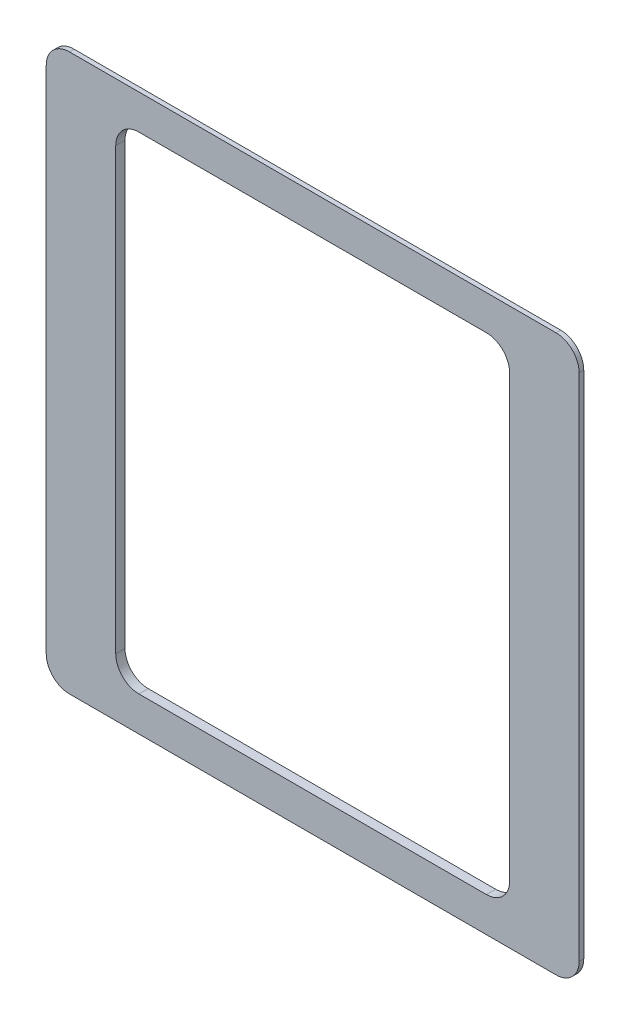
SolidWorks part; units mm, degrees
ref_plane "Front Plane" through (0, 0, 0) normal (0, 0, 1) x (1, 0, 0)
ref_plane "Top Plane" through (0, 0, 0) normal (0, 1, 0) x (1, 0, 0)
ref_plane "Right Plane" through (0, 0, 0) normal (1, 0, 0) x (0, 0, -1)
sketch "Sketch1" plane through (0, 0, 0) normal (0, 0, 1) x (1, 0, 0)
  line L1 (115, 120) -> (-115, 120)
  line L2 (115, 120) -> (115, -120)
  line L3 (115, -120) -> (-115, -120)
  line L4 (-115, 120) -> (-115, -120)
  line L5 (115, 120) -> (-115, -120) construction
  line L6 (115, -120) -> (-115, 120) construction
  line L7 (85, 105) -> (-85, 105)
  line L8 (85, 105) -> (85, -105)
  line L9 (85, -105) -> (-85, -105)
  line L10 (-85, 105) -> (-85, -105)
  line L11 (85, 105) -> (-85, -105) construction
  line L12 (85, -105) -> (-85, 105) construction
  point P0 (0, 0)
  point P6 (0, 0)
  dimension "D1" = 230
  dimension "D2" = 240
  dimension "D3" = 210
  dimension "D4" = 170
extrude "Boss-Extrude1" add sketch "Sketch1" along normal blind 2
fillet "Fillet1" radius 10 8 edges at (115, 120, 1) (85, 105, 1) (-85, 105, 1) (85, -105, 1) (-85, -105, 1) (-115, -120, 1) (115, -120, 1) (-115, 120, 1)
sketch "Sketch2" plane through (0, 0, 0) normal (0, 0, -1) x (-1, 0, 0)
  line L0 (75, -105) -> (-75, -105) construction
  line L1 (85, 95) -> (85, -95) construction
  line L2 (-75, 105) -> (75, 105) construction
  line L3 (-85, -95) -> (-85, 95) construction
  line L4 (75, -105) -> (-75, -105)
  line L5 (85, 95) -> (85, -95)
  line L6 (-75, 105) -> (75, 105)
  line L7 (-85, -95) -> (-85, 95)
  line L8 (75, -108) -> (-75, -108)
  line L9 (-88, -95) -> (-88, 95)
  line L10 (-75, 108) -> (75, 108)
  line L11 (88, 95) -> (88, -95)
  arc A0 (-85, -95) -> (-75, -105) centre (-75, -95) ccw construction
  arc A1 (75, -105) -> (85, -95) centre (75, -95) ccw construction
  arc A2 (85, 95) -> (75, 105) centre (75, 95) ccw construction
  arc A3 (-75, 105) -> (-85, 95) centre (-75, 95) ccw construction
  arc A4 (-85, -95) -> (-75, -105) centre (-75, -95) ccw
  arc A5 (75, -105) -> (85, -95) centre (75, -95) ccw
  arc A6 (85, 95) -> (75, 105) centre (75, 95) ccw
  arc A7 (-75, 105) -> (-85, 95) centre (-75, 95) ccw
  arc A8 (-88, -95) -> (-75, -108) centre (-75, -95) ccw
  arc A9 (-75, 108) -> (-88, 95) centre (-75, 95) ccw
  arc A10 (88, 95) -> (75, 108) centre (75, 95) ccw
  arc A11 (75, -108) -> (88, -95) centre (75, -95) ccw
  dimension "D1" = 3
extrude "Boss-Extrude2" add sketch "Sketch2" along normal blind 2
sketch "Sketch3" plane through (0, 0, 0) normal (0, 1, 0) x (1, 0, 0)
  line L0 (-88, 2) -> (-93.5678, 7.5678)
  line L1 (-93.5678, 7.5678) -> (-94.5678, 7.5678)
  line L2 (-94.5678, 7.5678) -> (-94.5678, 0)
  line L3 (105, 0) -> (-105, 0) construction
  line L4 (-94.5678, 0) -> (-88, 0)
  line L5 (-88, 2) -> (-88, 0) construction
  line L6 (-88, 0) -> (-88, 2)
  dimension "D1" = 7.874
  dimension "D2" = 1
  dimension "D3" = 45
extrude "Boss-Extrude3" add sketch "Sketch3" along normal mid plane 210
sketch "Sketch4" plane through (0, 0, 0) normal (0, 0, -1) x (-1, 0, 0)
  line L0 (88, -105) -> (82.0901, -105)
  line L1 (82.0901, -105) -> (87.1846, -94.0887)
  line L2 (87.1846, -94.0887) -> (89.219, -94.0887)
  line L3 (89.219, -94.0887) -> (89.219, -105)
  line L4 (88, -105) -> (93.5678, -105) construction
  line L5 (89.219, -105) -> (88, -105)
extrude "Boss-Extrude4" add sketch "Sketch4" along normal up to surface (2 mm away) up to face at (0, 0, -2)
mirror "Mirror1" about plane through (0, 0, 0) normal (0, 1, 0) of "Boss-Extrude4"
mirror "Mirror2" about plane through (0, 0, 0) normal (1, 0, 0) of "Boss-Extrude3", "Boss-Extrude4", "Mirror1"
